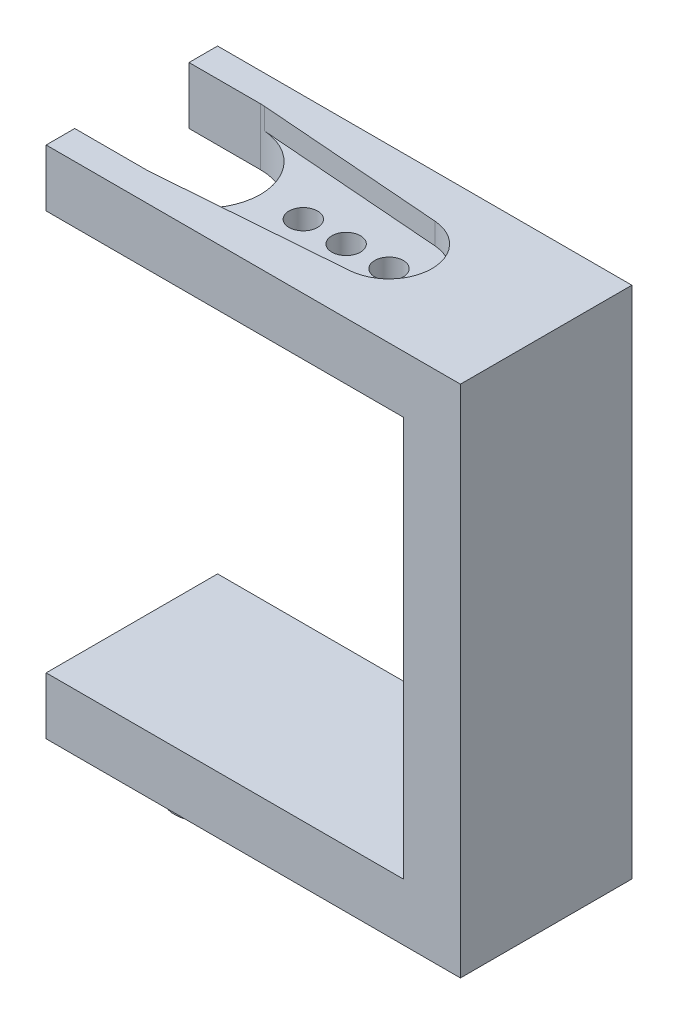
SolidWorks part; units mm, degrees
note: The reader was unsure of these and kept them because the rebuilt part matched: shared geometry of "草图4<3>".
ref_plane "前视基准面" through (0, 0, 0) normal (0, 0, 1) x (1, 0, 0)
ref_plane "上视基准面" through (0, 0, 0) normal (0, 1, 0) x (1, 0, 0)
ref_plane "右视基准面" through (0, 0, 0) normal (1, 0, 0) x (0, 0, -1)
other "Configuration Table"
sketch "草图1" plane through (0, 0, 0) normal (0, 0, 1) x (1, 0, 0)
  line L0 (0, 0) -> (25, 0)
  line L1 (25, 0) -> (25, 28)
  line L2 (25, 28) -> (0, 28)
  line L3 (0, 0) -> (0, 28) construction
  line L4 (0, -4) -> (29, -4)
  line L5 (29, -4) -> (29, 32)
  line L6 (29, 32) -> (0, 32)
  line L7 (0, 32) -> (0, 28)
  line L8 (0, 0) -> (0, -4)
  dimension "D1" = 28
  dimension "D2" = 25
  dimension "D3" = 4
extrude "凸台-拉伸1" add sketch "草图1" along normal blind 12
sketch "草图2" plane through (0, -4, 0) normal (0, -1, 0) x (1, 0, 0)
  line L0 (0, 6) -> (5, 6) construction
  line L1 (0, 12) -> (0, 0) construction
  circle A0 centre (5, 6) radius 2
  dimension "D2" = 4
  dimension "D1" = 5
sketch "草图3" plane through (0, 32, 0) normal (0, 1, 0) x (1, 0, 0)
  line L0 (0, -6) -> (5, -6) construction
  line L1 (0, -12) -> (0, 0) construction
  line L2 (5, -2) -> (0, -2)
  line L3 (5, -10) -> (0, -10)
  line L4 (0, -2) -> (0, -10)
  arc A0 (5, -10) -> (5, -2) centre (5, -6) ccw
  arc A1 (5, -2) -> (1, -6) centre (5, -6) ccw construction
  arc A2 (1, -6) -> (5, -10) centre (5, -6) ccw construction
  dimension "D2" = 8
  dimension "D1" = 5
extrude "切除-拉伸1" cut sketch "草图3" against normal blind 5.1
sketch "草图4" plane through (0, 32, 0) normal (0, 1, 0) x (1, 0, 0)
  line L0 (5, -6) -> (18, -6) construction
  line L1 (5.3077, -2.0119) -> (18.2308, -3.0089)
  line L2 (5.3077, -9.9881) -> (18.2308, -8.9911)
  circle A0 centre (18, -6) radius 3
  arc A1 (5, -10) -> (5, -2) centre (5, -6) ccw construction
  arc A2 (5, -10) -> (5, -2) centre (5, -6) ccw
  circle A3 centre (12, -6) radius 1
  circle A4 centre (15, -6) radius 1
  circle A5 centre (18, -6) radius 1
  dimension "D2" = 6
  dimension "D5" = 2
  dimension "D6" = 2
  dimension "D7" = 2
  dimension "D1" = 13
  dimension "D3" = 7
  dimension "D4" = 3
extrude "切除-拉伸2" cut sketch "草图4" against normal blind 1.5
extrude "切除-拉伸3" cut sketch "草图4<3>" against normal blind 6.5
sketch "草图4<3>" plane through (0, 32, 0) normal (0, 1, 0) x (1, 0, 0) same geometry as "草图4"
extrude "凸台-拉伸2" add sketch "草图2" along normal blind 4.1
